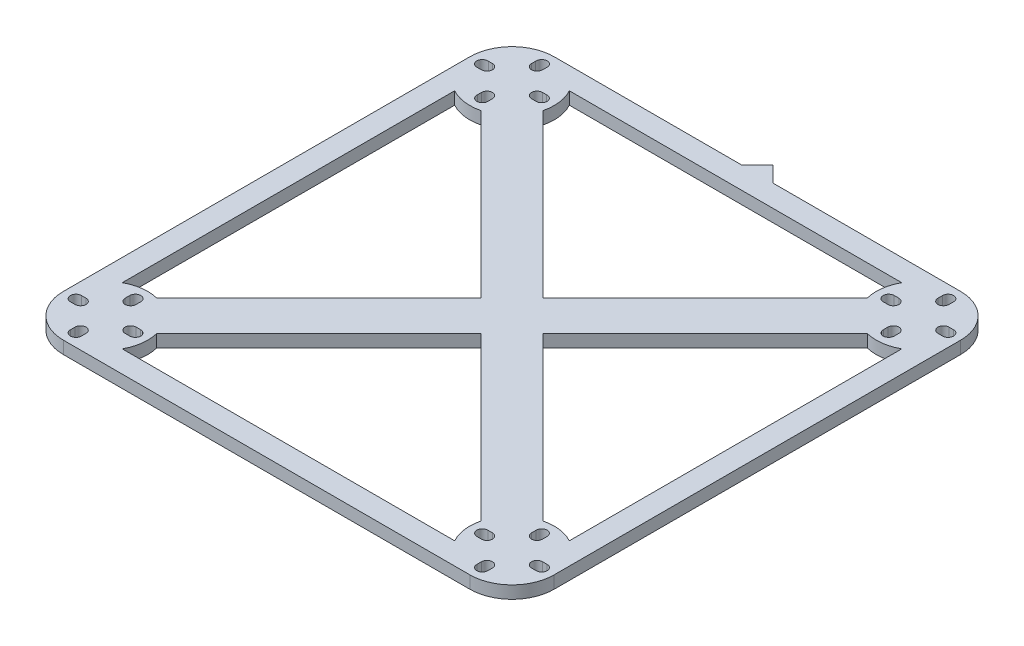
SolidWorks part; units mm, degrees
ref_plane "Front Plane" through (0, 0, 0) normal (0, 0, 1) x (1, 0, 0)
ref_plane "Top Plane" through (0, 0, 0) normal (0, 1, 0) x (1, 0, 0)
ref_plane "Right Plane" through (0, 0, 0) normal (1, 0, 0) x (0, 0, -1)
sketch "Sketch1" plane through (0, 0, 0) normal (0, 1, 0) x (1, 0, 0)
  line L0 (0, 78.5) -> (0, -78.5) construction
  line L1 (-78.5, 78.5) -> (78.5, 78.5)
  line L2 (-78.5, 78.5) -> (-78.5, -78.5)
  line L3 (-78.5, -78.5) -> (78.5, -78.5)
  line L4 (78.5, 78.5) -> (78.5, -78.5)
  line L5 (-78.5, 78.5) -> (78.5, -78.5) construction
  line L6 (-78.5, -78.5) -> (78.5, 78.5) construction
  line L7 (78.5, 0) -> (-78.5, 0) construction
  line L8 (-1, 65) -> (-1, 0) construction
  line L9 (-83.4497, 73.5503) -> (73.5503, -83.4497)
  line L10 (-73.5503, 83.4497) -> (83.4497, -73.5503)
  line L11 (-73.5503, -83.4497) -> (83.4497, 73.5503)
  line L12 (-83.4497, -73.5503) -> (73.5503, 83.4497)
  line L13 (-53.1678, 71.5) -> (53.1678, 71.5)
  line L14 (-53.1678, -71.5) -> (53.1678, -71.5)
  line L15 (71.5, -53.1678) -> (71.5, 53.1678)
  line L16 (-71.5, -53.1678) -> (-71.5, 53.1678)
  circle A0 centre (-65, 65) radius 13.5
  circle A1 centre (-65, 65) radius 64
  circle A2 centre (65, 65) radius 13.5
  circle A3 centre (-65, -65) radius 13.5
  circle A4 centre (65, -65) radius 13.5
  point P0 (0, 0)
  dimension "D1" = 27
  dimension "D2" = 128
  dimension "D3" = 2
  dimension "D4" = 14
  dimension "D5" = 7
extrude "Base shape" add sketch "Sketch1" along normal blind 4 contours L12 A3 L11 L9 | A4 L10 L11 L9 | L11 A2 L12 L10 | L9 A1 L10 A0 | A1 L9 L12 L10 | L12 L9 L11 L10 | L13 A1 L1 A0 | L13 A2 L1 A1 | A4 L4 A2 L15 | A4 L14 A3 L3 | L2 A3 L16 A1 | L2 A1 L16 A0 | A0 | A2 | A4 | A3 region at (-29.268, 0, -75.0845) region at (-75.0845, 0, -29.268) region at (27.4447, 0, -75.1014) region at (-37.8705, 0, -37.8705) region at (-75.1014, 0, 27.4447) region at (-12.3929, 0, -12.3929) region at (30.427, 0, -30.427) region at (0, 0, 0) region at (-30.427, 0, 30.427) region at (30.427, 0, 30.427) region at (75.0932, 0, 0) region at (0, 0, 75.0932)
sketch "Sketch2" plane through (0, 4, 0) normal (0, 1, 0) x (1, 0, 0)
  line L0 (-65, 74.5) -> (-65, 55.5) construction
  line L1 (-74.5, 65) -> (-55.5, 65) construction
  line L2 (0, 78.5) -> (0, -78.5) construction
  line L3 (-65, 78.5) -> (65, 78.5) construction
  line L4 (-65, -78.5) -> (65, -78.5) construction
  line L5 (-78.5, 0) -> (78.5, 0) construction
  line L6 (-78.5, 65) -> (-78.5, -65) construction
  line L7 (78.5, 65) -> (78.5, -65) construction
  line L8 (-66.75, 74.5) -> (-66.75, 73)
  line L9 (-63.25, 74.5) -> (-63.25, 73)
  line L10 (-74.5, 66.75) -> (-73, 66.75)
  line L11 (-74.5, 63.25) -> (-73, 63.25)
  line L12 (-66.75, 57) -> (-66.75, 55.5)
  line L13 (-63.25, 57) -> (-63.25, 55.5)
  line L14 (-57, 66.75) -> (-55.5, 66.75)
  line L15 (-57, 63.25) -> (-55.5, 63.25)
  line L16 (63.25, 57) -> (63.25, 55.5)
  line L17 (66.75, 57) -> (66.75, 55.5)
  line L18 (74.5, 63.25) -> (73, 63.25)
  line L19 (74.5, 66.75) -> (73, 66.75)
  line L20 (63.25, 74.5) -> (63.25, 73)
  line L21 (66.75, 74.5) -> (66.75, 73)
  line L22 (57, 66.75) -> (55.5, 66.75)
  line L23 (57, 63.25) -> (55.5, 63.25)
  line L24 (-66.75, -57) -> (-66.75, -55.5)
  line L25 (-63.25, -57) -> (-63.25, -55.5)
  line L26 (-57, -63.25) -> (-55.5, -63.25)
  line L27 (-57, -66.75) -> (-55.5, -66.75)
  line L28 (-74.5, -63.25) -> (-73, -63.25)
  line L29 (-74.5, -66.75) -> (-73, -66.75)
  line L30 (-63.25, -74.5) -> (-63.25, -73)
  line L31 (-66.75, -74.5) -> (-66.75, -73)
  line L32 (57, -63.25) -> (55.5, -63.25)
  line L33 (57, -66.75) -> (55.5, -66.75)
  line L34 (66.75, -74.5) -> (66.75, -73)
  line L35 (63.25, -74.5) -> (63.25, -73)
  line L36 (74.5, -66.75) -> (73, -66.75)
  line L37 (74.5, -63.25) -> (73, -63.25)
  line L38 (66.75, -57) -> (66.75, -55.5)
  line L39 (63.25, -57) -> (63.25, -55.5)
  circle A0 centre (-65, 65) radius 9.5
  circle A1 centre (-65, 65) radius 8
  circle A2 centre (-65, 74.5) radius 1.75
  circle A3 centre (-65, 55.5) radius 1.75
  circle A4 centre (-57, 65) radius 1.75
  circle A5 centre (-73, 65) radius 1.75
  circle A6 centre (-65, 73) radius 1.75
  circle A7 centre (-55.5, 65) radius 1.75
  circle A8 centre (-74.5, 65) radius 1.75
  circle A9 centre (-65, 57) radius 1.75
  circle A10 centre (65, 57) radius 1.75
  circle A11 centre (65, 55.5) radius 1.75
  circle A12 centre (73, 65) radius 1.75
  circle A13 centre (74.5, 65) radius 1.75
  circle A14 centre (65, 73) radius 1.75
  circle A15 centre (65, 74.5) radius 1.75
  circle A16 centre (57, 65) radius 1.75
  circle A17 centre (55.5, 65) radius 1.75
  circle A18 centre (-65, -57) radius 1.75
  circle A19 centre (-65, -55.5) radius 1.75
  circle A20 centre (-57, -65) radius 1.75
  circle A21 centre (-55.5, -65) radius 1.75
  circle A22 centre (-74.5, -65) radius 1.75
  circle A23 centre (-73, -65) radius 1.75
  circle A24 centre (-65, -74.5) radius 1.75
  circle A25 centre (-65, -73) radius 1.75
  circle A26 centre (55.5, -65) radius 1.75
  circle A27 centre (57, -65) radius 1.75
  circle A28 centre (65, -74.5) radius 1.75
  circle A29 centre (65, -73) radius 1.75
  circle A30 centre (74.5, -65) radius 1.75
  circle A31 centre (73, -65) radius 1.75
  circle A32 centre (65, -55.5) radius 1.75
  circle A33 centre (65, -57) radius 1.75
  dimension "D1" = 19
  dimension "D2" = 16
  dimension "D3" = 3.5
extrude "Motor mounting holes" cut sketch "Sketch2" against normal up to next contours A27 A26 | A26 A27 | A27 A26 | A27 L32 A26 | A27 A26 L33 | A29 A28 | A28 A29 | A28 A29 | A29 L35 A28 | A29 A28 L34 | A31 A30 | A30 A31 | A31 A30 | A31 A30 L37 | A31 L36 A30 | A33 A32 | A32 A33 | A33 A32 | A33 A32 L39 | A33 L38 A32 | A17 A16 | A17 A16 | A16 A17 | L22 A17 A16 | A16 A17 L23 | A11 A10 | A11 A10 | A10 A11 | L16 A11 A10 | A10 A11 L17 | A12 A13 | A13 A12 | A13 A12 | A12 A13 L19 | L18 A13 A12 | A14 A15 | A15 A14 | A15 A14 | A14 A15 L20 | L21 A15 A14 | A8 A5 L10 A0 | A8 A0 L11 A5 | A6 A2 A0 L8 | A6 L9 A0 A2 | A7 A4 L15 A0 | A7 A0 L14 A4 | A9 L12 A0 A3 | A9 A3 A0 L13 | A19 A18 | A19 A18 | A18 A19 | A18 A19 L24 | L25 A19 A18 | A22 A23 | A23 A22 | A23 A22 | A22 A23 L28 | L29 A23 A22 | A21 A20 | A21 A20 | A20 A21 | A20 A21 L26 | L27 A21 A20 | A24 A25 | A25 A24 | A25 A24 | A24 A25 L31 | L30 A25 A24 | A8 | A5 | A2 | A6 | A4 | A7 | A9 | A3 region at (-66.6996, 4, -73.7469) region at (-73.7469, 4, -66.6996) region at (-63.3004, 4, -73.7469) region at (-56.2531, 4, -66.6996) region at (-73.7469, 4, -63.3004) region at (-66.6996, 4, -56.2531) region at (-56.2531, 4, -63.3004) region at (-63.3004, 4, -56.2531) region at (63.3002, 4, -56.25) region at (65, 4, -57.6692) region at (65, 4, -54.8308) region at (66.6998, 4, -56.25) region at (65, 4, -56.25) region at (75.1692, 4, -65) region at (73.75, 4, -63.3002) region at (72.3308, 4, -65) region at (73.75, 4, -65) region at (73.75, 4, -66.6998) region at (63.3002, 4, -73.75) region at (65, 4, -75.1692) region at (65, 4, -72.3308) region at (66.6998, 4, -73.75) region at (65, 4, -73.75) region at (56.25, 4, -66.6998) region at (57.6692, 4, -65) region at (54.8308, 4, -65) region at (56.25, 4, -65) region at (56.25, 4, -63.3002) region at (-65, 4, 57.6692) region at (-66.6998, 4, 56.25) region at (-65, 4, 54.8308) region at (-63.3002, 4, 56.25) region at (-65, 4, 56.25) region at (-57.6692, 4, 65) region at (-56.25, 4, 63.3002) region at (-54.8308, 4, 65) region at (-56.25, 4, 66.6998) region at (-56.25, 4, 65) region at (-75.1692, 4, 65) region at (-73.75, 4, 63.3002) region at (-72.3308, 4, 65) region at (-73.75, 4, 66.6998) region at (-73.75, 4, 65) region at (-63.3002, 4, 73.75) region at (-65, 4, 75.1692) region at (-65, 4, 72.3308) region at (-66.6998, 4, 73.75) region at (-65, 4, 73.75) region at (56.25, 4, 63.3002) region at (57.6692, 4, 65) region at (54.8308, 4, 65) region at (56.25, 4, 65) region at (56.25, 4, 66.6998) region at (66.6998, 4, 73.75) region at (65, 4, 75.1692) region at (65, 4, 72.3308) region at (63.3002, 4, 73.75) region at (65, 4, 73.75) region at (75.1692, 4, 65) region at (73.75, 4, 66.6998)
sketch "Sketch3" plane through (0, 0, 0) normal (0, -1, 0) x (1, 0, 0)
  line L0 (0, -71.5) -> (0, -83.5) construction
  line L1 (-53.1678, -71.5) -> (53.1678, -71.5) construction
  line L2 (-65, -78.5) -> (65, -78.5) construction
  line L3 (0, -83.5) -> (-5, -78.5)
  line L4 (-5, -78.5) -> (5, -78.5)
  line L5 (0, -83.5) -> (5, -78.5)
  point P10 (0, -78.5)
  dimension "D1" = 5
  dimension "D2" = 45
extrude "Forward arrow" add sketch "Sketch3" against normal up to surface (4 mm away) contours L4 L0 L5 | L0 L4 L3 region at (1.6667, 0, -80.1667) region at (-1.6667, 0, -80.1667) up to face at (65, 4, 73.75)
equation "\"MotorDiameter\"=27"
equation "\"D1@Sketch1\"=\"MotorDiameter\""
equation "\"PropDiameter\"=128"
equation "\"D2@Sketch1\"=\"PropDiameter\""
equation "\"PropDistance\"=2"
equation "\"D3@Sketch1\"=\"PropDistance\""
equation "\"ArmWidth\"=14"
equation "\"D4@Sketch1\"=\"ArmWidth\""
equation "\"FrameDepth\"=4"
equation "\"D1@Base shape\" = \"FrameDepth\""
equation "\"D5@Sketch1\"=\"ArmWidth\"/2"
equation "\"MotorHoleOuterDiameter\"=19"
equation "\"D1@Sketch2\"=\"MotorHoleOuterDiameter\""
equation "\"MotorHoleInnerDiameter\"=16"
equation "\"D2@Sketch2\"=\"MotorHoleInnerDiameter\""
equation "\"MotorHoleDiameter\"=3.5"
equation "\"D3@Sketch2\"=\"MotorHoleDiameter\""
